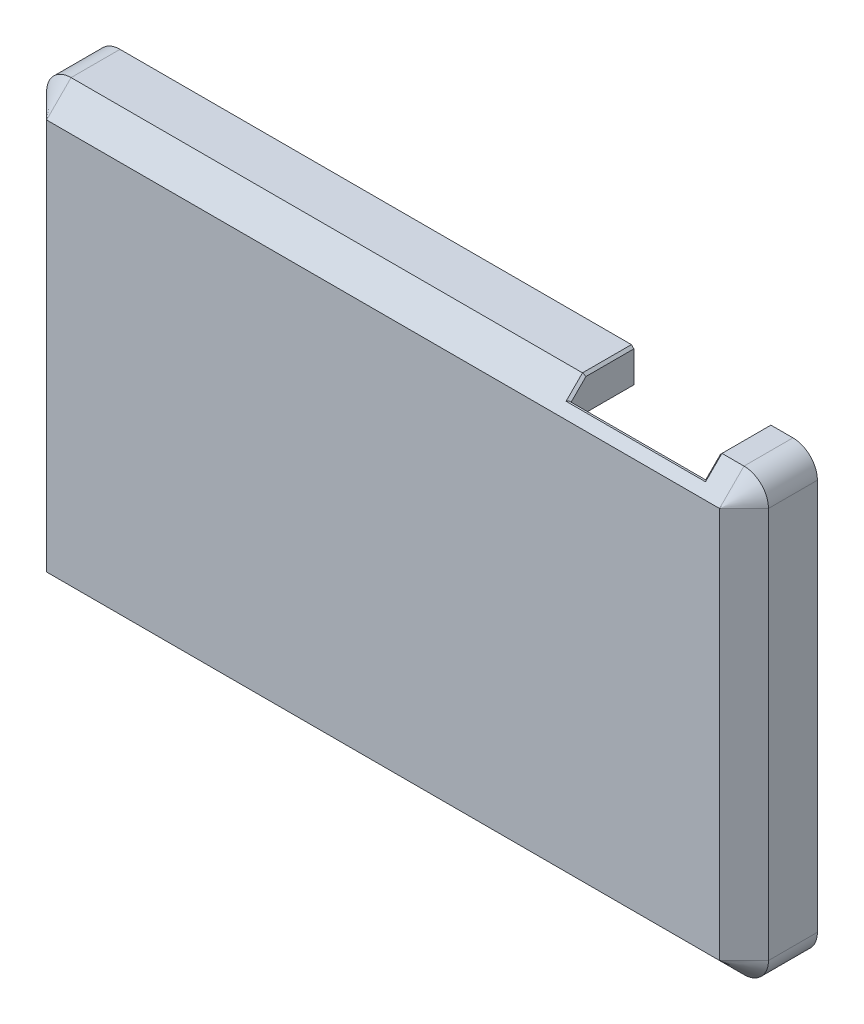
SolidWorks part; units mm, degrees
material "1060 合金"
ref_plane "前视基准面" through (0, 0, 0) normal (0, 0, 1) x (1, 0, 0)
ref_plane "上视基准面" through (0, 0, 0) normal (0, 1, 0) x (1, 0, 0)
ref_plane "右视基准面" through (0, 0, 0) normal (1, 0, 0) x (0, 0, -1)
sketch "草图1" plane through (0, 0, 0) normal (0, 0, 1) x (1, 0, 0)
  line L1 (-29.5, -18) -> (29.5, -18)
  line L2 (-29.5, -18) -> (-29.5, 18)
  line L3 (-29.5, 18) -> (29.5, 18)
  line L4 (29.5, -18) -> (29.5, 18)
  line L5 (-29.5, -18) -> (29.5, 18) construction
  line L6 (-29.5, 18) -> (29.5, -18) construction
  point P0 (0, 0)
  dimension "D1" = 59
  dimension "D2" = 36
extrude "凸台-拉伸1" add sketch "草图1" along normal blind 6
sketch "草图2" plane through (0, 0, 0) normal (0, 0, -1) x (-1, 0, 0)
  line L1 (-26.75, -15.25) -> (26.75, -15.25)
  line L2 (-26.75, -15.25) -> (-26.75, 15.25)
  line L3 (-26.75, 15.25) -> (26.75, 15.25)
  line L4 (26.75, -15.25) -> (26.75, 15.25)
  line L5 (-26.75, -15.25) -> (26.75, 15.25) construction
  line L6 (-26.75, 15.25) -> (26.75, -15.25) construction
  point P0 (0, 0)
  dimension "D1" = 53.5
  dimension "D2" = 30.5
extrude "切除-拉伸1" cut sketch "草图2" against normal blind 5.2
fillet "圆角1" radius 2 4 edges at (-29.5, 18, 3) (-29.5, -18, 3) (29.5, 18, 3) (29.5, -18, 3)
sketch "草图3" plane through (0, 0, 5.2) normal (0, 0, -1) x (-1, 0, 0)
  line L0 (26.75, 15.25) -> (-26.75, 15.25) construction
  line L1 (15.75, 15.25) -> (11.75, 15.25)
  line L2 (15.75, 15.25) -> (15.75, -15.25)
  line L3 (15.75, -15.25) -> (11.75, -15.25)
  line L4 (11.75, 15.25) -> (11.75, -15.25)
  line L5 (-26.75, -15.25) -> (26.75, -15.25) construction
  line L7 (26.75, -15.25) -> (26.75, 15.25) construction
  dimension "D1" = 4
  dimension "D2" = 11
extrude "凸台-拉伸2" add sketch "草图3" along normal blind 3.7
fillet "圆角2" radius 4 4 edges at (-15.75, -15.25, 3.35) (-11.75, -15.25, 3.35) (-15.75, 15.25, 3.35) (-11.75, 15.25, 3.35)
chamfer "倒角1" distance 2 angle 45 8 edges at (0, -18, 6) (28.9142, -17.4142, 6) (-28.9142, -17.4142, 6) (29.5, 0, 6) (-29.5, 0, 6) (28.9142, 17.4142, 6) (-28.9142, 17.4142, 6) (0, 18, 6)
sketch "草图4" plane through (0, 18, 0) normal (0, 1, 0) x (1, 0, 0)
  line L0 (29.5, 0) -> (29.5, -4) construction
  line L1 (14.5, 0) -> (25.5, 0)
  line L2 (14.5, 0) -> (14.5, -5.2)
  line L3 (14.5, -5.2) -> (25.5, -5.2)
  line L4 (25.5, 0) -> (25.5, -5.2)
  line L5 (14.5, 0) -> (25.5, -5.2) construction
  line L6 (14.5, -5.2) -> (25.5, 0) construction
  line L7 (27.5, 0) -> (-27.5, 0) construction
  point P0 (20, -2.6)
  dimension "D1" = 11
  dimension "D2" = 4
  dimension "D3" = 5.2
extrude "切除-拉伸2" cut sketch "草图4" against normal blind 10
fillet "圆角3" radius 0.2 4 edges at (26.75, -15.25, 2.6) (26.75, 15.25, 2.6) (-26.75, -15.25, 2.6) (-26.75, 15.25, 2.6)
chamfer "倒角2" distance 0.2 angle 45 5 edges at (25.5, 18, 2) (25.5, 17.4, 4.6) (20, 16.8, 5.2) (14.5, 17.4, 4.6) (14.5, 18, 2) first distance on face at (26.5, 18, 2) first distance on face at (10, 17.2, 4.8) first distance on face at (-6.5, 18, 2)
sketch "草图5" plane through (0, 0, 0) normal (0, 0, -1) x (-1, 0, 0)
  line L1 (-27.5, -16.5) -> (27.5, -16.5) construction
  line L2 (-27.5, -16.5) -> (-27.5, 16.5) construction
  line L3 (-27.5, 16.5) -> (27.5, 16.5) construction
  line L4 (27.5, -16.5) -> (27.5, 16.5) construction
  line L5 (-27.5, -16.5) -> (27.5, 16.5) construction
  line L6 (-27.5, 16.5) -> (27.5, -16.5) construction
  point P0 (0, 0)
  dimension "D1" = 55
  dimension "D2" = 33
hole_wizard "M1.2x0.25 螺纹孔1" positions "3D草图1" profile "草图6" tap size "M1.2x0.25" standard "GB"
sketch3d "3D草图1"
  point P0 (27.5, 16.5, 0)
  point P3 (27.5, -16.5, 0)
  point P6 (-27.5, -16.5, 0)
  point P12 (-27.5, 16.5, 0)
sketch "草图6" plane through (27.5, 16.5, 0) normal (1, 0, 0) x (0, 1, 0)
  line L0 (0, 0) -> (0, 3.2854)
  line L1 (0, 3.2854) -> (0.475, 3)
  line L2 (0.475, 3) -> (0.475, 0)
  line L5 (0.475, 0) -> (0, 0)
  line L10 (0, 3.2854) -> (-0.475, 3) construction
  line L11 (0, -6.35) -> (0, 107.95) construction
  dimension "螺纹孔钻头直径" = 0.95
  dimension "螺纹孔钻头深度" = 3
  dimension "导头角度" = 118
cosmetic thread "孔螺蚊线5" parameters "D1"=2.4, "D2"=1.2
cosmetic thread "孔螺蚊线6" parameters "D1"=2.4, "D2"=1.2
cosmetic thread "孔螺蚊线7" parameters "D1"=2.4, "D2"=1.2
cosmetic thread "孔螺蚊线8" parameters "D1"=2.4, "D2"=1.2
